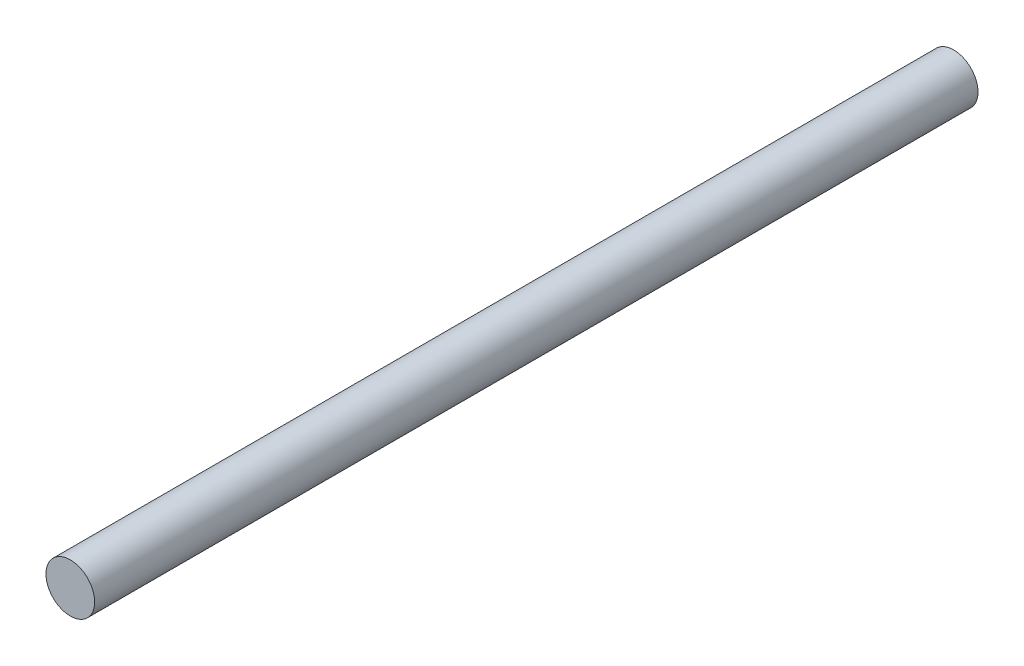
SolidWorks part; units mm, degrees
ref_plane "前视基准面" through (0, 0, 0) normal (0, 0, 1) x (1, 0, 0)
ref_plane "上视基准面" through (0, 0, 0) normal (0, 1, 0) x (1, 0, 0)
ref_plane "右视基准面" through (0, 0, 0) normal (1, 0, 0) x (0, 0, -1)
other "Configuration Table"
sketch "Sketch1" plane through (0, 0, 0) normal (0, 0, 1) x (1, 0, 0)
  circle A0 centre (0, 0) radius 20
extrude "Boss-Extrude1" add sketch "Sketch1" along normal blind 725
ref_plane "face_top" through (0, 0, 725) normal (0, 0, 1) x (1, 0, 0)
ref_plane "face_bottom" through (0, 0, 0) normal (0, 0, 1) x (1, 0, 0)
sketch3d "3DSketch1"
  line L0 (0, 0, 0) -> (0, 0, 725) construction
ref_axis "axis_center" through (0, 0, 0) along (0, 0, 1)
